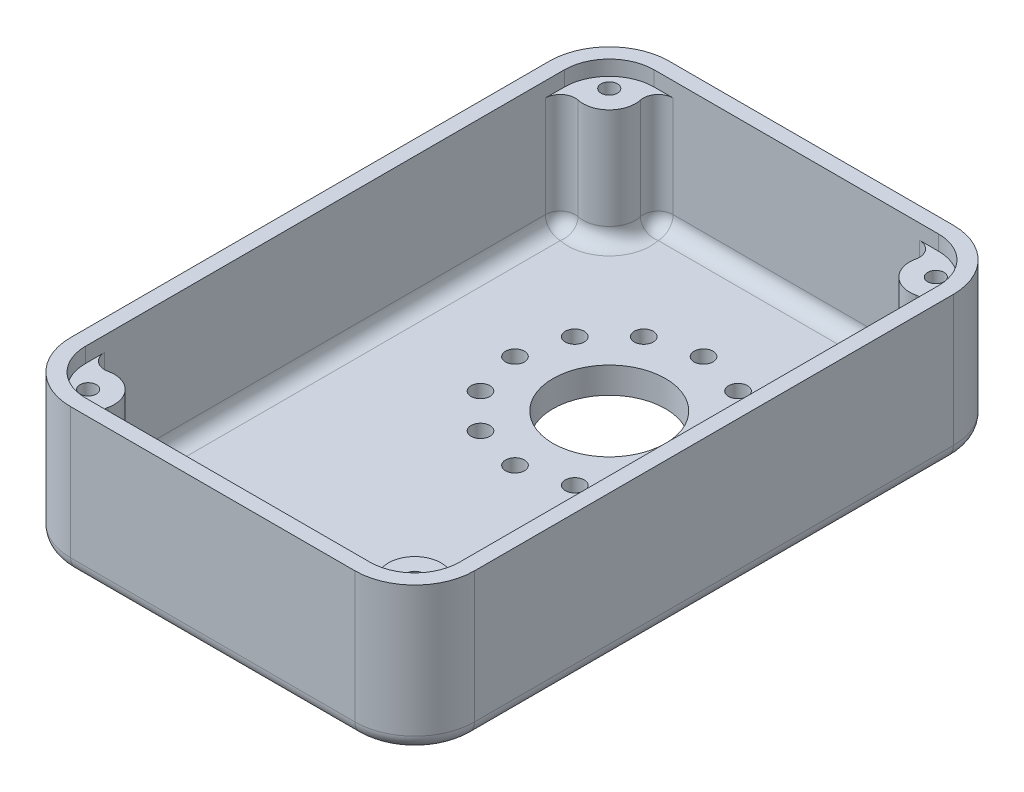
SolidWorks part; units mm, degrees
ref_plane "Front Plane" through (0, 0, 0) normal (0, 0, 1) x (1, 0, 0)
ref_plane "Top Plane" through (0, 0, 0) normal (0, 1, 0) x (1, 0, 0)
ref_plane "Right Plane" through (0, 0, 0) normal (1, 0, 0) x (0, 0, -1)
sketch "Sketch1" plane through (0, 0, 0) normal (0, 0, 1) x (1, 0, 0)
  line L0 (0, 0) -> (0, 10.3527) construction
  line L1 (-9.5504, 0) -> (-20.574, 0)
  line L2 (-20.574, 0) -> (-20.574, -1.905)
  line L3 (-20.574, -1.905) -> (-9.5504, -1.905)
  line L6 (-9.5504, -1.905) -> (-9.5504, 0)
  point P5 (-9.5504, -5.08)
  point P8 (-9.6567, -5.08)
  dimension "D1" = 20.574
  dimension "D2" = 9.5504
  dimension "D4" = 1.905
revolve "Revolve1" add sketch "Sketch1" angle 360 about L0
sketch "Sketch4" plane through (0, 0, 0) normal (0, 1, 0) x (1, 0, 0)
  line L0 (0, 0) -> (0, -36.4153) construction
  line L1 (-34.29, -16.51) -> (34.29, -16.51) construction
  line L2 (24.13, -67.31) -> (-24.13, -67.31)
  line L3 (34.29, -57.15) -> (34.29, 24.13)
  line L4 (24.13, 34.29) -> (-24.13, 34.29)
  line L5 (-34.29, -57.15) -> (-34.29, 24.13)
  line L6 (34.29, -67.31) -> (-34.29, 34.29) construction
  line L7 (34.29, 34.29) -> (-34.29, -67.31) construction
  line L8 (-24.13, -57.15) -> (0, -33.02) construction
  circle A0 centre (0, 0) radius 20.574 construction
  circle A1 centre (0, 0) radius 9.5504
  circle A2 centre (0, 0) radius 28.2956 construction
  circle A3 centre (0, 0) radius 30.8356 construction
  arc A4 (-34.29, -57.15) -> (-24.13, -67.31) centre (-24.13, -57.15) ccw
  arc A5 (24.13, -67.31) -> (34.29, -57.15) centre (24.13, -57.15) ccw
  arc A6 (34.29, 24.13) -> (24.13, 34.29) centre (24.13, 24.13) ccw
  arc A7 (-24.13, 34.29) -> (-34.29, 24.13) centre (-24.13, 24.13) ccw
  point P3 (0, -16.51)
  dimension "D3" = 34.29
  dimension "D4" = 2.54
  dimension "D5" = 10.16
  dimension "D1" = 68.58
  dimension "D2" = 101.6
  dimension "D6" = 135
extrude "Boss-Extrude1" add sketch "Sketch4" along normal blind 2.54
hole_wizard "M3 Clearance Hole1" positions "Sketch3" profile "Sketch2" hole size "M3" standard "ANSI Metric" end condition through all
sketch "Sketch3" plane through (0, 2.54, 0) normal (0, 1, 0) x (1, 0, 0)
  line L0 (0, 0) -> (0, 1.3105) construction
  line L2 (0, 0) -> (-5.7425, 0) construction
  circle A0 centre (0, 0) radius 16.002 construction
  point P6 (-16.002, 0)
  point P15 (-13.8581, 8.001)
  point P16 (-8.001, 13.8581)
  point P34 (0, 16.002)
  point P35 (8.001, 13.8581)
  point P36 (13.8581, 8.001)
  point P37 (16.002, 0)
  point P38 (13.8581, -8.001)
  point P39 (8.001, -13.8581)
  point P40 (0, -16.002)
  point P41 (-8.001, -13.8581)
  point P42 (-13.8581, -8.001)
  dimension "D1" = 32.004
  dimension "D2" = 12
sketch "Sketch2" plane through (-13.8581, 2.54, 8.001) normal (1, 0, 0) x (0, 0, 1)
  line L0 (0, 0) -> (0, 4.445)
  line L1 (0, 4.445) -> (1.6, 4.445)
  line L2 (1.6, 4.445) -> (1.6, 0)
  line L5 (1.6, 0) -> (0, 0)
  line L11 (0, -6.35) -> (0, 107.95) construction
  dimension "Thru Hole Dia." = 3.2
  dimension "Thru Hole Depth" = 4.445
sketch "Sketch6" plane through (0, 2.54, 0) normal (0, 1, 0) x (1, 0, 0)
  line L6 (24.13, 34.29) -> (-24.13, 34.29)
  line L7 (-34.29, 24.13) -> (-34.29, -57.15)
  line L8 (-24.13, -67.31) -> (24.13, -67.31)
  line L9 (34.29, -57.15) -> (34.29, 24.13)
  line L10 (24.13, 31.75) -> (-24.13, 31.75)
  line L19 (31.75, -57.15) -> (31.75, 24.13)
  line L20 (-24.13, -64.77) -> (24.13, -64.77)
  line L21 (-31.75, 24.13) -> (-31.75, -57.15)
  line L22 (24.13, 31.75) -> (-24.13, 31.75)
  line L23 (31.75, -57.15) -> (31.75, 24.13)
  line L24 (-24.13, -64.77) -> (24.13, -64.77)
  line L25 (-31.75, 24.13) -> (-31.75, -57.15)
  arc A5 (-24.13, 34.29) -> (-34.29, 24.13) centre (-24.13, 24.13) ccw
  arc A6 (-34.29, -57.15) -> (-24.13, -67.31) centre (-24.13, -57.15) ccw
  arc A14 (24.13, -67.31) -> (34.29, -57.15) centre (24.13, -57.15) ccw
  arc A15 (34.29, 24.13) -> (24.13, 34.29) centre (24.13, 24.13) ccw
  arc A16 (31.75, 24.13) -> (24.13, 31.75) centre (24.13, 24.13) ccw
  arc A17 (-24.13, 31.75) -> (-31.75, 24.13) centre (-24.13, 24.13) ccw
  arc A18 (24.13, -64.77) -> (31.75, -57.15) centre (24.13, -57.15) ccw
  arc A19 (-31.75, -57.15) -> (-24.13, -64.77) centre (-24.13, -57.15) ccw
  arc A20 (31.75, 24.13) -> (24.13, 31.75) centre (24.13, 24.13) ccw
  arc A21 (-24.13, 31.75) -> (-31.75, 24.13) centre (-24.13, 24.13) ccw
  arc A22 (24.13, -64.77) -> (31.75, -57.15) centre (24.13, -57.15) ccw
  arc A23 (-31.75, -57.15) -> (-24.13, -64.77) centre (-24.13, -57.15) ccw
  dimension "D1" = 2.54
  dimension "D2" = 2.54
extrude "Boss-Extrude4" add sketch "Sketch6" along normal blind 22.225
fillet "Fillet1" radius 2.54 8 edges at (-31.3142, 0, 64.3342) (-34.29, 0, 16.51) (-31.3142, 0, -31.3142) (0, 0, -34.29) (31.3142, 0, -31.3142) (34.29, 0, 16.51) (31.3142, 0, 64.3342) (0, 0, 67.31)
sketch "Sketch8" plane through (0, 2.54, 0) normal (0, 1, 0) x (1, 0, 0)
  line L0 (-24.13, -57.15) -> (-46.8517, -79.8717) construction
  line L1 (-34.29, 24.13) -> (-34.29, -57.15) construction
  line L2 (0, -64.77) -> (0, 31.75) construction
  line L3 (-24.13, -64.77) -> (24.13, -64.77) construction
  line L4 (24.13, 31.75) -> (-24.13, 31.75) construction
  line L5 (0, -16.51) -> (-37.3684, -16.51) construction
  circle A0 centre (-27.7221, -60.7421) radius 4.445
  circle A1 centre (-27.7221, -60.7421) radius 1.3891
  circle A3 centre (27.7221, -60.7421) radius 1.3891
  circle A5 centre (27.7221, -60.7421) radius 4.445
  circle A6 centre (27.7221, 27.7221) radius 1.3891
  circle A7 centre (27.7221, 27.7221) radius 4.445
  circle A8 centre (-27.7221, 27.7221) radius 1.3891
  circle A9 centre (-27.7221, 27.7221) radius 4.445
  dimension "D2" = 2.7781
  dimension "D3" = 8.89
  dimension "D1" = 45
  dimension "D4" = 5.08
extrude "Boss-Extrude5" add sketch "Sketch8" along normal offset from surface (19.685 mm away) 2.54 up to face at (0, 24.765, 16.51)
fillet "Fillet3" radius 2.54 8 edges at (25.5718, 12.3825, 64.6324) (31.6124, 12.3825, 58.5918) (25.5718, 12.3825, -31.6124) (31.6124, 12.3825, -25.5718) (-31.6124, 12.3825, -25.5718) (-25.5718, 12.3825, -31.6124) (-31.6124, 12.3825, 58.5918) (-25.5718, 12.3825, 64.6324)
fillet "Fillet4" radius 2.54 16 edges at (-30.8033, 2.54, -22.8755) (-24.579, 2.54, -24.579) (-22.8755, 2.54, -30.8033) (0, 2.54, -31.75) (22.8755, 2.54, -30.8033) (24.579, 2.54, -24.579) (30.8033, 2.54, -22.8755) (31.75, 2.54, 16.51) (30.8033, 2.54, 55.8955) (24.579, 2.54, 57.599) (22.8755, 2.54, 63.8233) (0, 2.54, 64.77) (-22.8755, 2.54, 63.8233) (-24.579, 2.54, 57.599) (-30.8033, 2.54, 55.8955) (-31.75, 2.54, 16.51)
